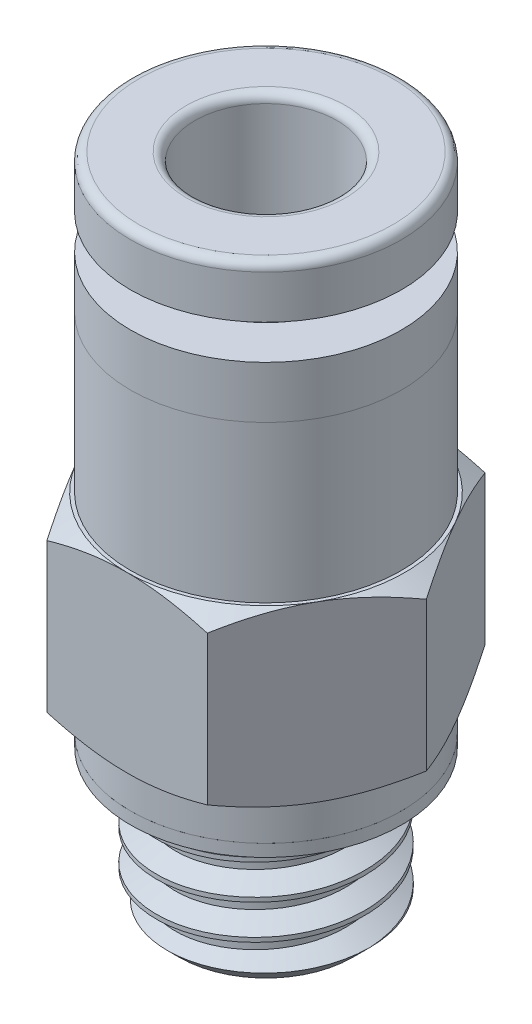
SolidWorks part; units mm, degrees
ref_plane "Front Plane" through (0, 0, 0) normal (0, 0, 1) x (1, 0, 0)
ref_plane "Top Plane" through (0, 0, 0) normal (0, 1, 0) x (1, 0, 0)
ref_plane "Right Plane" through (0, 0, 0) normal (1, 0, 0) x (0, 0, -1)
sketch "Sketch1" plane through (0, 0, 0) normal (0, 1, 0) x (1, 0, 0)
  line L1 (2.3094, -4) -> (4.6188, 0)
  line L2 (4.6188, 0) -> (2.3094, 4)
  line L3 (2.3094, 4) -> (-2.3094, 4)
  line L4 (-2.3094, 4) -> (-4.6188, 0)
  line L5 (-4.6188, 0) -> (-2.3094, -4)
  line L6 (-2.3094, -4) -> (2.3094, -4)
  circle A1 centre (0, 0) radius 4 construction
  dimension "D1" = 8
extrude "Boss-Extrude1" add sketch "Sketch1" along normal mid plane 5
sketch "Sketch2" plane through (0, 2.5, 0) normal (0, 1, 0) x (1, 0, 0)
  line L0 (-2.3094, -4) -> (2.3094, -4) construction
  circle A0 centre (0, 0) radius 4
extrude "Cut-Extrude1" cut sketch "Sketch2" against normal blind 5 draft 60 flip side to cut
mirror "Mirror1" about plane through (0, 0, 0) normal (0, 1, 0) of "Cut-Extrude1"
sketch "Sketch3" plane through (0, 2.5, 0) normal (0, 1, 0) x (1, 0, 0)
  circle A0 centre (0, 0) radius 3.9
  dimension "D1" = 7.8
extrude "Boss-Extrude2" add sketch "Sketch3" along normal blind 4.5
sketch "Sketch4" plane through (0, 7, 0) normal (0, 1, 0) x (1, 0, 0)
  circle A1 centre (0, 0) radius 3.9
  circle A2 centre (0, 0) radius 3.9
  dimension "D1" = 0
extrude "Boss-Extrude3" add sketch "Sketch4" along normal blind 4 separate body
ref_plane "Plane2" through (0, 9, 0) normal (0, 1, 0) x (1, 0, 0)
sketch "Sketch6" plane through (0, 9, 0) normal (0, 1, 0) x (1, 0, 0)
  circle A0 centre (0, 0) radius 2.5
  dimension "D1" = 5
extrude "Cut-Extrude2" cut sketch "Sketch6" against normal mid plane 1 flip side to cut
sketch "Sketch7" plane through (0, 11, 0) normal (0, 1, 0) x (1, 0, 0)
  circle A0 centre (0, 0) radius 2.05
  dimension "D1" = 4.1
extrude "Cut-Extrude3" cut sketch "Sketch7" against normal blind 12
sketch "Sketch8" plane through (0, -2.5, 0) normal (0, -1, 0) x (1, 0, 0)
  circle A0 centre (0, 0) radius 3.9 construction
  circle A1 centre (0, 0) radius 3.9
extrude "Boss-Extrude4" add sketch "Sketch8" along normal blind 1
sketch "Sketch9" plane through (0, -3.5, 0) normal (0, -1, 0) x (1, 0, 0)
  circle A0 centre (0, 0) radius 3
  dimension "D1" = 6
extrude "Boss-Extrude5" add sketch "Sketch9" along normal blind 4.35
sketch "Sketch10" plane through (0, -3.5, 0) normal (0, -1, 0) x (1, 0, 0)
  circle A0 centre (0, 0) radius 3 construction
  circle A1 centre (0, 0) radius 3.9
  circle A2 centre (0, 0) radius 3.9
  circle A3 centre (0, 0) radius 3
  dimension "D1" = 0
extrude "Boss-Extrude6" add sketch "Sketch10" along normal blind 0.35 separate body
chamfer "Chamfer1" distance 0.5 angle 45 1 edges at (0, -7.85, -3)
thread "Thread1" pitch 1 method cut trim with start face yes profile "Thread Profile1" start angle 0, offset 1, length 0, pitch 1, diameter 6
ref_plane "Plane3" through (3, -8.35, 0) normal (0, 0, 1) x (1, 0, 0)
sketch "Thread Profile1" plane through (3, -8.35, 0) normal (0, 0, 1) x (1, 0, 0)
  line L0 (0, 0) -> (0, 1) construction
  line L11 (0, 0) -> (0, 0.875)
  line L12 (0, 0.875) -> (-0.5413, 0.5625)
  line L13 (-0.5413, 0.5625) -> (-0.5413, 0.3125)
  line L15 (-0.5413, 0.3125) -> (0, 0)
  line L17 (-0.5413, 0.4375) -> (0, 0.4375) construction
  point P2 (0, 0)
  dimension "Pitch" = 1
  dimension "Profile_Angle" = 60
  dimension "Profile_Land" = 0.25
  dimension "Profile_Height" = 0.5413
sketch "Sketch14" plane through (0, -7.85, 0) normal (0, -1, 0) x (1, 0, 0)
  circle A0 centre (0, 0) radius 1.2
  dimension "D1" = 2.4
extrude "Cut-Extrude4" cut sketch "Sketch14" against normal through all
chamfer "Chamfer2" distance 0.1 angle 45 1 edges at (0, -7.85, -1.2)
fillet "Fillet1" radius 0.25 2 edges at (0, 11, 3.9) (0, 11, 2.05)
